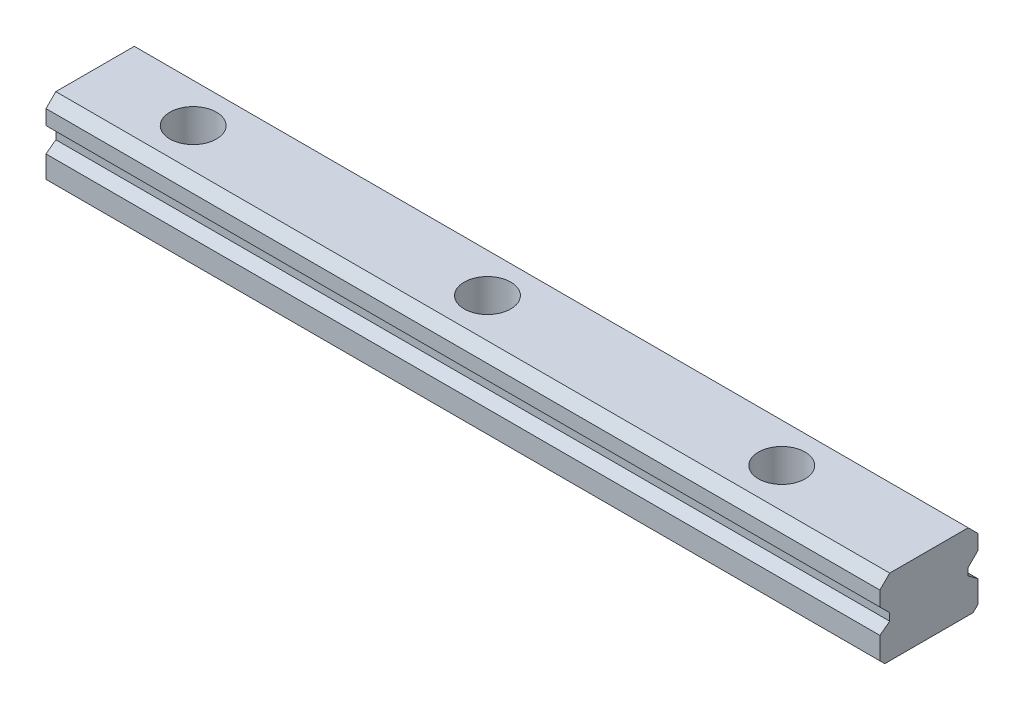
SolidWorks part; units mm, degrees
material "201 Annealed Stainless Steel (SS)"
ref_plane "Front Plane" through (0, 0, 0) normal (0, 0, 1) x (1, 0, 0)
ref_plane "Top Plane" through (0, 0, 0) normal (0, 1, 0) x (1, 0, 0)
ref_plane "Right Plane" through (0, 0, 0) normal (1, 0, 0) x (0, 0, -1)
sketch "Sketch1" plane through (0, 0, 0) normal (1, 0, 0) x (0, 0, -1)
  line L0 (0, 39.5089) -> (0, 0) construction
  line L1 (9, 0) -> (-9, 0)
  line L2 (-9, 0) -> (-10, 1)
  line L3 (-10, 1) -> (-10, 5.5)
  line L4 (-10, 5.5) -> (-8, 7)
  line L5 (-8, 7) -> (-8, 8.5)
  line L6 (-8, 8.5) -> (-10, 10.5)
  line L7 (-10, 10.5) -> (-10, 13.5)
  line L8 (-10, 13.5) -> (-8, 15.5)
  line L9 (-8, 15.5) -> (8, 15.5)
  line L10 (-18.0832, 7.75) -> (13.0406, 7.75) construction
  line L11 (-4.25, 15.5) -> (-4.25, 7) construction
  line L12 (-4.25, 7) -> (-3, 7) construction
  line L13 (-3, 7) -> (-3, 0) construction
  line L14 (4.25, 15.5) -> (4.25, 7) construction
  line L15 (4.25, 7) -> (3, 7) construction
  line L16 (3, 7) -> (3, 0) construction
  line L17 (9, 0) -> (10, 1)
  line L18 (10, 1) -> (10, 5.5)
  line L19 (10, 5.5) -> (8, 7)
  line L20 (8, 7) -> (8, 8.5)
  line L21 (8, 8.5) -> (10, 10.5)
  line L22 (10, 13.5) -> (8, 15.5)
  line L23 (10, 10.5) -> (10, 13.5)
  point P14 (-8, 7.75)
  point P32 (0, 15.5)
  dimension "D1" = 10
  dimension "D2" = 1
  dimension "D3" = 1
  dimension "D4" = 5.5
  dimension "D5" = 7.75
  dimension "D6" = 15.5
  dimension "D7" = 4.25
  dimension "D8" = 3
  dimension "D9" = 8.5
  dimension "D10" = 7
  dimension "D11" = 2
  dimension "D12" = 2
  dimension "D13" = 2
  dimension "D14" = 2
extrude "Boss-Extrude1" add sketch "Sketch1" along normal blind 170
sketch "Sketch2" plane through (0, 15.5, 0) normal (0, 1, 0) x (1, 0, 0)
  line L0 (0, 0) -> (170, 0) construction
  line L1 (0, 8) -> (0, -8) construction
  line L2 (170, 8) -> (170, -8) construction
  circle A0 centre (20, 0) radius 4.75
  dimension "D1" = 9.5
  dimension "D2" = 20
extrude "Cut-Extrude1" cut sketch "Sketch2" against normal blind 8.5
sketch "Sketch3" plane through (0, 7, 0) normal (0, 1, 0) x (1, 0, 0)
  circle A0 centre (20, 0) radius 3
  dimension "D1" = 6
extrude "Cut-Extrude2" cut sketch "Sketch3" against normal through all
pattern_linear "LPattern1" count 3 spacing 60 along (1, 0, 0) of "Cut-Extrude2", "Cut-Extrude1"
